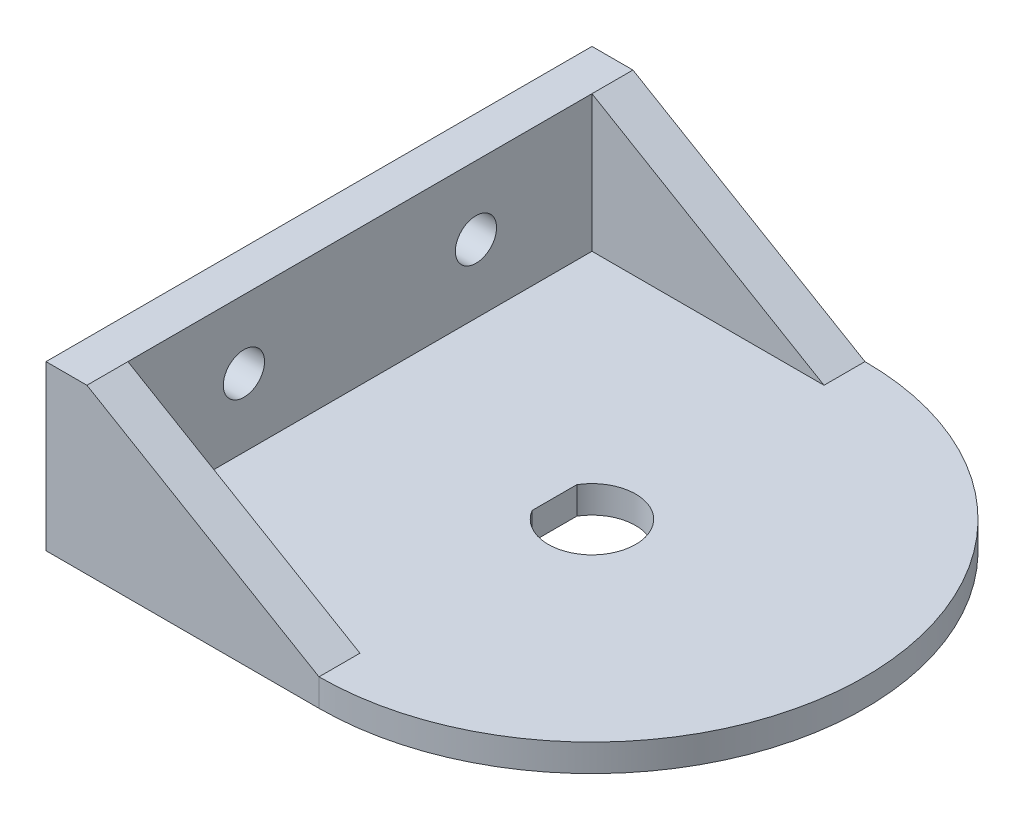
SolidWorks part; units mm, degrees
ref_plane "Front Plane" through (0, 0, 0) normal (0, 0, 1) x (1, 0, 0)
ref_plane "Top Plane" through (0, 0, 0) normal (0, 1, 0) x (1, 0, 0)
ref_plane "Right Plane" through (0, 0, 0) normal (1, 0, 0) x (0, 0, -1)
sketch "Sketch1" plane through (0, 0, 0) normal (0, 1, 0) x (1, 0, 0)
  line L0 (0, 0) -> (0, 20)
  line L1 (0, 20) -> (-20, 20)
  line L2 (-20, 20) -> (-20, 0)
  line L3 (-20, 0) -> (-20, -20)
  line L4 (-20, -20) -> (0, -20)
  line L5 (0, -20) -> (0, 0)
  line L6 (-20, 20) -> (-17, 20)
  line L7 (-17, 20) -> (-17, -20)
  line L8 (-17, -20) -> (-20, -20)
  circle A0 centre (0, 0) radius 3.2
  circle A1 centre (0, 0) radius 20
extrude "Boss-Extrude1" add sketch "Sketch1" along normal blind 2 contours L0 A1 L7 L5 A0 | L5 A1 L0 A0 | A1 L7 L4 | A1 L3 L4 L7 | L7 A1 | A1 L7 L1 L2 | A1 L1 L7 region at (-7.9588, 0, 0) region at (8.6756, 0, 0) region at (-12.9768, 0, -17.3298) region at (-12.9768, 0, 17.3298) region at (-18.662, 0, -13.3322) region at (-18.2081, 0, 0) region at (-18.662, 0, 13.3322)
extrude "Boss-Extrude2" add sketch "Sketch1<4>" along normal blind 12 contours A1 L7 L1 L2 | L7 A1 | A1 L3 L4 L7 region at (-18.662, 0, -13.3322) region at (-18.2081, 0, 0) region at (-18.662, 0, 13.3322)
sketch "Sketch1<4>" plane through (0, 0, 0) normal (0, 1, 0) x (1, 0, 0) same geometry as "Sketch1"
sketch "Sketch2" plane through (0, 0, 20) normal (0, 0, 1) x (1, 0, 0)
  line L0 (-17, 12) -> (0, 2)
  line L1 (0, 2) -> (-17, 2)
  line L2 (-17, 2) -> (-17, 12)
extrude "Boss-Extrude3" add sketch "Sketch2" against normal blind 3
sketch "Sketch3" plane through (0, 0, -20) normal (0, 0, -1) x (-1, 0, 0)
  line L0 (17, 12) -> (0, 2)
  line L1 (0, 2) -> (17, 2)
  line L2 (17, 2) -> (17, 12)
extrude "Boss-Extrude4" add sketch "Sketch3" against normal blind 3
sketch "Sketch4" plane through (0, 2, 0) normal (0, 1, 0) x (1, 0, 0)
  line L0 (3.2, 0) -> (-2.75, 0)
  line L1 (-2.75, 0) -> (-2.75, 1.6363)
  line L2 (-2.75, 0) -> (-2.75, -1.6363)
  circle A0 centre (0, 0) radius 3.2 construction
  arc A1 (-2.75, 1.6363) -> (-2.75, -1.6363) centre (0, 0) ccw
  circle M7 centre (0, 0) radius 3.2
extrude "Boss-Extrude5" add sketch "Sketch4" against normal up to surface (2 mm away) contours L2 L1 M7 region at (-2.9311, 2, 0) up to face at (-5, 0, 0)
sketch "Sketch5" plane through (-17, 0, 0) normal (1, 0, 0) x (0, 0, -1)
  line L1 (-17, 12) -> (-17, 2) construction
  line L2 (17, 2) -> (17, 12) construction
  line L3 (0, 7) -> (17, 7)
  line L4 (0, 7) -> (-17, 7)
  circle A0 centre (-8.5, 7) radius 1.51
  circle A1 centre (8.5, 7) radius 1.51
  point P6 (0, 7)
extrude "Cut-Extrude1" cut sketch "Sketch5" against normal blind 3 contours L4 A0 | L4 A0 | L3 A1 | L3 A1 region at (-17, 7.6409, -8.5) region at (-17, 6.3591, -8.5) region at (-17, 6.3591, 8.5) region at (-17, 7.6409, 8.5)
